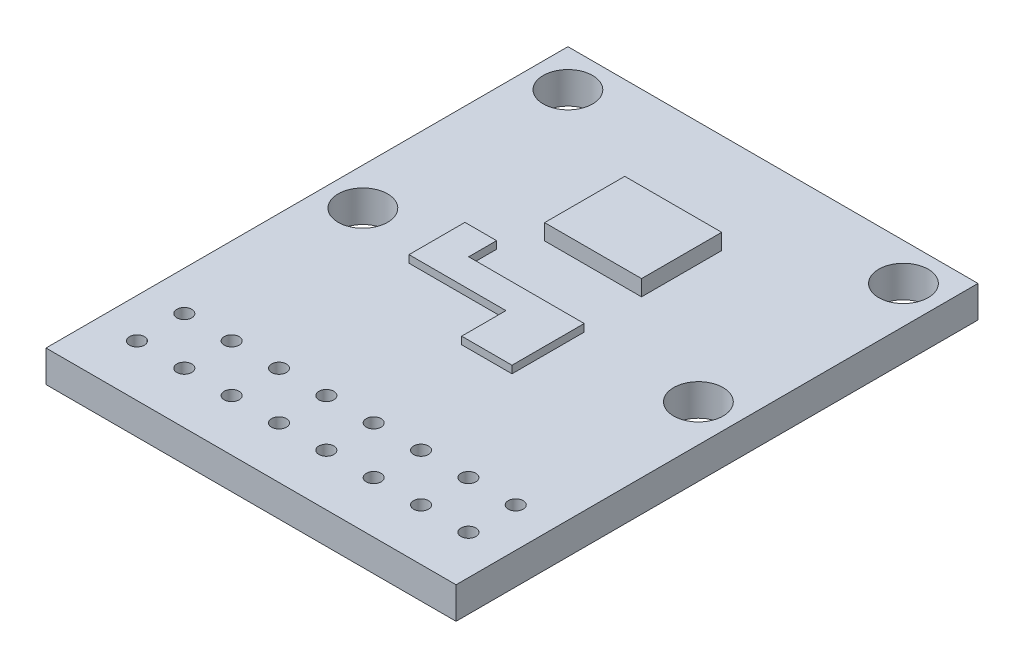
SolidWorks part; units mm, degrees
ref_plane "Front Plane" through (0, 0, 0) normal (0, 0, 1) x (1, 0, 0)
ref_plane "Top Plane" through (0, 0, 0) normal (0, 1, 0) x (1, 0, 0)
ref_plane "Right Plane" through (0, 0, 0) normal (1, 0, 0) x (0, 0, -1)
sketch "Sketch1" plane through (0, 0, 0) normal (0, 1, 0) x (1, 0, 0)
  line L0 (-11, -7.5) -> (-11, -20.5)
  line L1 (-11, -7.5) -> (11, -7.5) construction
  line L2 (-11, -7.5) -> (-11, 7.5)
  line L3 (-11, 7.5) -> (11, 7.5)
  line L4 (11, -7.5) -> (11, 7.5)
  line L5 (-11, -7.5) -> (11, 7.5) construction
  line L6 (-11, 7.5) -> (11, -7.5) construction
  line L7 (-11, -20.5) -> (11, -20.5)
  line L8 (11, -20.5) -> (11, -7.5)
  point P0 (0, 0)
  dimension "D1" = 22
  dimension "D2" = 15
  dimension "D3" = 28
extrude "Boss-Extrude1" add sketch "Sketch1" along normal mid plane 1.7
sketch "Sketch2" plane through (0, 0.85, 0) normal (0, 1, 0) x (1, 0, 0)
  line L0 (0, 0) -> (0, 7.5) construction
  line L1 (-11, 7.5) -> (11, -7.5) construction
  line L2 (-11, 7.5) -> (11, 7.5) construction
  line L3 (0, 0) -> (-11, 0) construction
  line L4 (-11, -7.5) -> (-11, 7.5) construction
  line L5 (-11, -20.5) -> (11, -20.5) construction
  line L6 (-10.16, -13.92) -> (10.16, -13.92) construction
  line L7 (-10.16, -13.92) -> (-10.16, -19) construction
  line L8 (-10.16, -19) -> (10.16, -19) construction
  line L9 (10.16, -13.92) -> (10.16, -19) construction
  line L10 (-10.16, -13.92) -> (10.16, -19) construction
  line L11 (-10.16, -19) -> (10.16, -13.92) construction
  circle A0 centre (-9, 5.5) radius 1.325
  circle A1 centre (9, 5.5) radius 1.325
  circle A2 centre (9, -5.5) radius 1.325
  circle A3 centre (-9, -5.5) radius 1.325
  circle A4 centre (-8.89, -15.19) radius 0.4
  circle A5 centre (-6.35, -15.19) radius 0.4
  circle A6 centre (-3.81, -15.19) radius 0.4
  circle A7 centre (-1.27, -15.19) radius 0.4
  circle A8 centre (1.27, -15.19) radius 0.4
  circle A9 centre (3.81, -15.19) radius 0.4
  circle A10 centre (6.35, -15.19) radius 0.4
  circle A11 centre (8.89, -15.19) radius 0.4
  circle A12 centre (-6.35, -17.73) radius 0.4
  circle A13 centre (-3.81, -17.73) radius 0.4
  circle A14 centre (-1.27, -17.73) radius 0.4
  circle A15 centre (1.27, -17.73) radius 0.4
  circle A16 centre (3.81, -17.73) radius 0.4
  circle A17 centre (6.35, -17.73) radius 0.4
  circle A18 centre (8.89, -17.73) radius 0.4
  circle A19 centre (-8.89, -17.73) radius 0.4
  point P13 (-8.0783, -17.5968)
  point P18 (0, -16.46)
  dimension "D3" = 2.65
  dimension "D7" = 0.8
  dimension "D1" = 2
  dimension "D2" = 2
  dimension "D4" = 20.32
  dimension "D5" = 5.08
  dimension "D6" = 1.5
  dimension "D8" = 1.27
  dimension "D9" = 1.27
  dimension "D12" = 2.54
  dimension "D13" = 2.54
  dimension "D10" = 8
  dimension "D11" = 2
extrude "Cut-Extrude1" cut sketch "Sketch2" against normal through all
sketch "Sketch3" plane through (0, 0.85, 0) normal (0, 1, 0) x (1, 0, 0)
  line L1 (2.6, -2.15) -> (-2.6, -2.15)
  line L2 (2.6, -2.15) -> (2.6, 2.15)
  line L3 (2.6, 2.15) -> (-2.6, 2.15)
  line L4 (-2.6, -2.15) -> (-2.6, 2.15)
  line L5 (2.6, -2.15) -> (-2.6, 2.15) construction
  line L6 (2.6, 2.15) -> (-2.6, -2.15) construction
  line L7 (-5.2, -3.825) -> (-5.2, -6.825)
  line L8 (-5.2, -6.825) -> (0, -6.825)
  line L9 (0, -6.825) -> (0, -9.2)
  line L10 (0, -9.2) -> (2.7, -9.2)
  line L11 (2.7, -9.2) -> (2.7, -5.325)
  line L12 (2.7, -5.325) -> (-3.5, -5.325)
  line L13 (-3.5, -5.325) -> (-3.5, -3.825)
  line L14 (-3.5, -3.825) -> (-5.2, -3.825)
  line L15 (-11, -7.5) -> (-11, -20.5) construction
  line L16 (11, -20.5) -> (11, -7.5) construction
  line L17 (-11, -20.5) -> (11, -20.5) construction
  circle A0 centre (-9, -5.5) radius 1.325 construction
  point P0 (0, 0)
  dimension "D1" = 5.2
  dimension "D2" = 4.3
  dimension "D3" = 5.8
  dimension "D4" = 3
  dimension "D5" = 8.3
  dimension "D6" = 11.3
  dimension "D7" = 1.7
  dimension "D8" = 1.5
extrude "Boss-Extrude2" add sketch "Sketch3" along normal blind 0.85 contours L1 L4 L3 L2
extrude "Boss-Extrude3" add sketch "Sketch3<3>" along normal blind 0.4 contours L8 L9 L10 L11 L12 L13 L14 L7
sketch "Sketch3<3>" plane through (0, 0.85, 0) normal (0, 1, 0) x (1, 0, 0) same geometry as "Sketch3"
